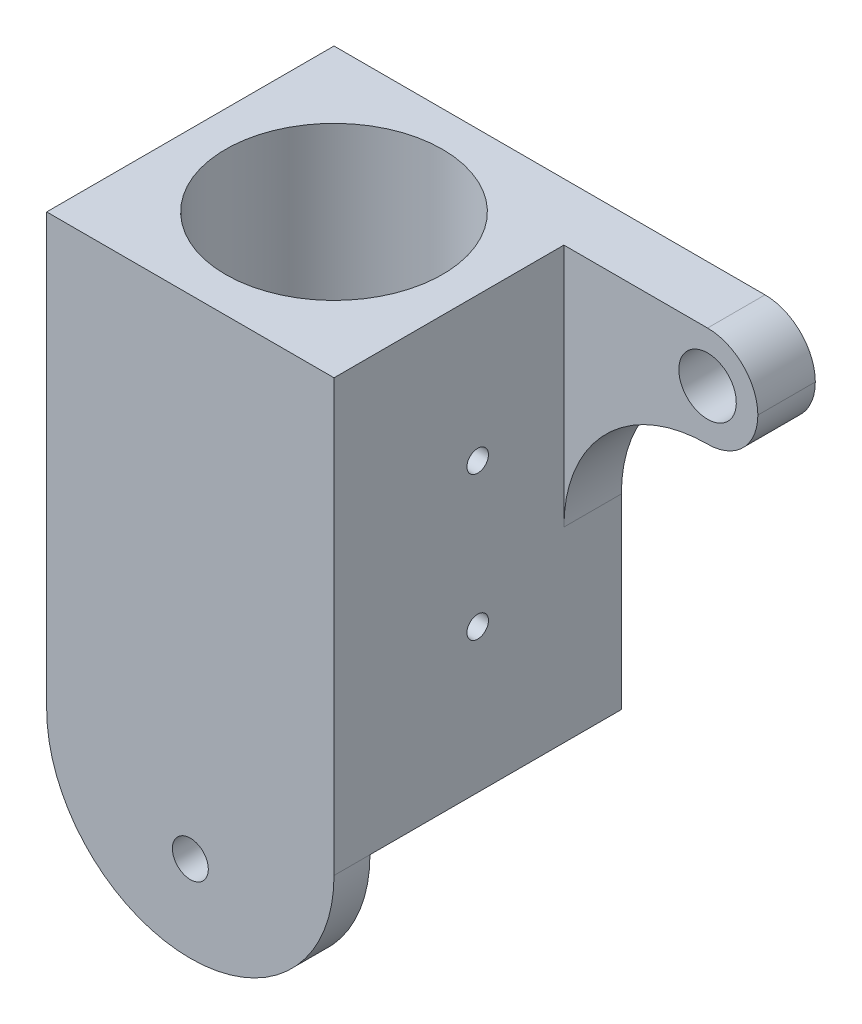
SolidWorks part; units mm, degrees
ref_plane "前基準面" through (0, 0, 0) normal (0, 0, 1) x (1, 0, 0)
ref_plane "上基準面" through (0, 0, 0) normal (0, 1, 0) x (1, 0, 0)
ref_plane "右基準面" through (0, 0, 0) normal (1, 0, 0) x (0, 0, -1)
sketch "草圖1" plane through (0, 0, 0) normal (0, 1, 0) x (1, 0, 0)
  line L1 (-20, 20) -> (20, 20)
  line L2 (-20, 20) -> (-20, -20)
  line L3 (-20, -20) -> (20, -20)
  line L4 (20, 20) -> (20, -20)
  line L5 (-20, 20) -> (20, -20) construction
  line L6 (-20, -20) -> (20, 20) construction
  dimension "D2" = 40
extrude "填料-伸長1" add sketch "草圖1" along normal blind 60
sketch "草圖2" plane through (0, 60, 0) normal (0, 1, 0) x (1, 0, 0)
  circle A0 centre (0, 0) radius 15.1
  dimension "D1" = 30.2
extrude "除料-伸長1" cut sketch "草圖2" against normal blind 50
sketch "草圖3" plane through (0, 0, 20) normal (0, 0, 1) x (1, 0, 0)
  line L0 (-20, 0) -> (20, 0)
  arc A0 (-20, 0) -> (20, 0) centre (0, 0) ccw
  circle A1 centre (0, -8) radius 2.5
  dimension "D1" = 5
  dimension "D2" = 8
extrude "填料-伸長2" add sketch "草圖3" against normal blind 5
sketch "草圖4" plane through (20, 0, 0) normal (1, 0, 0) x (0, 0, -1)
  circle A0 centre (0, 20) radius 1.5
  dimension "D1" = 3
  dimension "D2" = 20
extrude "除料-伸長2" cut sketch "草圖4" against normal through all
pattern_linear "直線複製排列1" count 2 spacing 20 along (0, 1, 0) of "除料-伸長2"
sketch "草圖5" plane through (20, 0, 0) normal (1, 0, 0) x (0, 0, -1)
  line L1 (20, 60) -> (12, 60)
  line L2 (20, 60) -> (20, 46)
  line L3 (20, 46) -> (12, 46)
  line L4 (12, 60) -> (12, 46)
  dimension "D1" = 8
  dimension "D2" = 14
extrude "填料-伸長3" add sketch "草圖5" along normal blind 27
fillet "圓角2" radius 7 2 edges at (47, 46, -16) (47, 60, -16)
sketch "草圖6" plane through (0, 0, -20) normal (0, 0, -1) x (-1, 0, 0)
  circle A0 centre (-40, 53) radius 4
  arc A1 (-40, 60) -> (-47, 53) centre (-40, 53) ccw construction
  dimension "D1" = 8
extrude "除料-伸長3" cut sketch "草圖6" against normal up to next
fillet "圓角3" radius 20 1 edges at (20, 46, -16)
